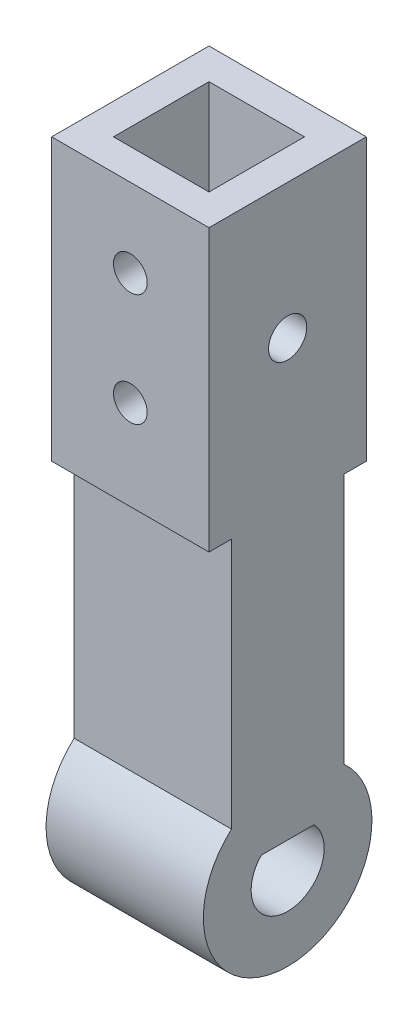
SolidWorks part; units mm, degrees
material "PLA"
ref_plane "Plan de face" through (0, 0, 0) normal (0, 0, 1) x (1, 0, 0)
ref_plane "Plan de dessus" through (0, 0, 0) normal (0, 1, 0) x (1, 0, 0)
ref_plane "Plan de droite" through (0, 0, 0) normal (1, 0, 0) x (0, 0, -1)
sketch "Esquisse1" plane through (0, 0, 0) normal (0, 0, 1) x (1, 0, 0)
  line L1 (0, 0) -> (140, 0) construction
  line L2 (0, 0) -> (0, 155) construction
  line L3 (0, 155) -> (140, 155) construction
  line L4 (140, 0) -> (140, 155) construction
  line L16 (65, 0) -> (65, 121.945)
  line L17 (65, 121.945) -> (0, 145.6031)
  line L18 (0, 145.6031) -> (3.4202, 155)
  line L19 (3.4202, 155) -> (70, 130.7669)
  line L20 (70, 130.7669) -> (136.5798, 155)
  line L21 (136.5798, 155) -> (140, 145.6031)
  line L22 (140, 145.6031) -> (75, 121.945)
  line L23 (75, 121.945) -> (75, 0)
  line L24 (75, 0) -> (65, 0)
  point P19 (70, 0)
  dimension "D1" = 140
  dimension "D2" = 155
  dimension "D3" = 10
  dimension "D4" = 70
  dimension "D5" = 110
  dimension "D6" = 110
  dimension "D7" = 140
  dimension "D8" = 10
  dimension "D9" = 10
  dimension "D10" = 70
extrude "Boss.-Extru.1" add sketch "Esquisse1" along normal blind 10
sketch "Esquisse2" plane through (0, 0, 0) normal (0, 0, -1) x (-1, 0, 0)
  line L0 (-75, 121.945) -> (-140, 145.6031) construction
  line L1 (-140, 145.6031) -> (-136.5798, 155) construction
  line L2 (-136.5798, 155) -> (-70, 130.7669) construction
  line L3 (-135.3015, 143.893) -> (-140, 145.6031)
  line L4 (-140, 145.6031) -> (-136.5798, 155)
  line L5 (-136.5798, 155) -> (-127.1829, 151.5798)
  line L6 (-128.893, 146.8813) -> (-127.1829, 151.5798)
  line L7 (0, 145.6031) -> (-65, 121.945) construction
  line L8 (-70, 130.7669) -> (-3.4202, 155) construction
  line L9 (-3.4202, 155) -> (0, 145.6031) construction
  line L10 (0, 145.6031) -> (-4.6985, 143.893)
  line L11 (-12.8171, 151.5798) -> (-3.4202, 155)
  line L12 (-3.4202, 155) -> (0, 145.6031)
  line L13 (-12.8171, 151.5798) -> (-11.107, 146.8813)
  line L14 (-135.3015, 143.893) -> (-128.893, 146.8813)
  line L15 (-11.107, 146.8813) -> (-4.6985, 143.893)
  dimension "D1" = 10
  dimension "D2" = 10
  dimension "D3" = 5
  dimension "D4" = 5
  dimension "D5" = 5
  dimension "D6" = 5
extrude "Boss.-Extru.2" add sketch "Esquisse2" along normal blind 15
fillet "Congé1" radius 20 3 edges at (75, 121.945, 5) (65, 121.945, 5) (70, 130.7669, 5)
fillet "Congé2" radius 4 2 edges at (138.2899, 150.3015, 10) (1.7101, 150.3015, 10)
sketch "Esquisse3" plane through (65, 0, 0) normal (-1, 0, 0) x (0, 0, 1)
  line L0 (5, 0) -> (5, 33.6289) construction
  line L1 (10, 0) -> (0, 0) construction
  circle A0 centre (5, 0) radius 7.5
  dimension "D1" = 15
extrude "Boss.-Extru.3" add sketch "Esquisse3" against normal up to surface (10 mm away) up to face at (75, 53.9704, 5)
sketch "Esquisse7" plane through (0, 0, 10) normal (0, 0, 1) x (1, 0, 0)
  line L0 (3.4202, 155) -> (0, 145.6031)
  line L1 (0, 145.6031) -> (51.8404, 126.7347)
  line L2 (65, 107.9409) -> (65, 27.9409)
  line L3 (65, 107.9409) -> (65, 5.5902) construction
  line L4 (65, 27.9409) -> (75, 27.9409)
  line L5 (75, 5.5902) -> (75, 107.9409) construction
  line L6 (75, 27.9409) -> (75, 107.9409)
  line L7 (88.1596, 126.7347) -> (140, 145.6031)
  line L8 (140, 145.6031) -> (136.5798, 155)
  line L9 (136.5798, 155) -> (76.8404, 133.2566)
  line L10 (63.1596, 133.2566) -> (3.4202, 155)
  arc A0 (51.8404, 126.7347) -> (65, 107.9409) centre (45, 107.9409) cw
  arc A1 (75, 107.9409) -> (88.1596, 126.7347) centre (95, 107.9409) cw
  arc A2 (76.8404, 133.2566) -> (63.1596, 133.2566) centre (70, 152.0505) cw
  dimension "D1" = 80
extrude "Enlèv. mat.-Extru.1" cut sketch "Esquisse7" against normal up to surface (25 mm away) up to face at (133.5914, 148.5914, -15)
sketch "Esquisse11" plane through (0, 27.9409, 0) normal (0, 1, 0) x (1, 0, 0)
  line L0 (65, 0) -> (65, -10) construction
  line L1 (61, 2) -> (75, 2)
  line L2 (61, 2) -> (61, -12)
  line L3 (61, -12) -> (75, -12)
  line L4 (75, 2) -> (75, -12)
  line L5 (65, -10) -> (75, -10) construction
  dimension "D1" = 14
  dimension "D2" = 14
  dimension "D3" = 4
  dimension "D4" = 2
extrude "Boss.-Extru.4" add sketch "Esquisse11" along normal blind 25
sketch "Esquisse12" plane through (0, 52.9409, 0) normal (0, 1, 0) x (1, 0, 0)
  line L0 (68, 2) -> (68, -12) construction
  line L1 (63.75, -0.75) -> (72.25, -0.75)
  line L2 (63.75, -0.75) -> (63.75, -9.25)
  line L3 (63.75, -9.25) -> (72.25, -9.25)
  line L4 (72.25, -0.75) -> (72.25, -9.25)
  line L5 (75, 2) -> (61, 2) construction
  line L6 (61, -12) -> (75, -12) construction
  line L7 (61, -5) -> (75, -5) construction
  line L8 (61, 2) -> (61, -12) construction
  line L9 (75, -12) -> (75, 2) construction
  line L10 (68, -0.75) -> (68, -9.25) construction
  line L11 (63.75, -5) -> (72.25, -5) construction
  dimension "D1" = 8.5
  dimension "D2" = 8.5
extrude "Enlèv. mat.-Extru.4" cut sketch "Esquisse12" against normal blind 20
sketch "Esquisse13" plane through (61, 0, 0) normal (-1, 0, 0) x (0, 0, 1)
  line L2 (12, 52.9409) -> (12, 27.9409) construction
  line L3 (-2, 52.9409) -> (12, 52.9409) construction
  circle A0 centre (5, 40.9409) radius 1.5
  dimension "D3" = 3
  dimension "D1" = 12
  dimension "D2" = 7
extrude "Enlèv. mat.-Extru.5" cut sketch "Esquisse13" against normal up to surface (14 mm away) up to face at (75, 26.9669, 5)
sketch "Esquisse4" plane through (65, 0, 0) normal (-1, 0, 0) x (0, 0, 1)
  line L7 (5, 0) -> (5, 7.4852) construction
  line L11 (2.6548, 2.25) -> (7.3452, 2.25)
  line L12 (0.3981, -3.25) -> (8.2082, -3.25) construction
  arc A1 (2.6548, 2.25) -> (7.3452, 2.25) centre (5, 0) ccw
  point P10 (5, 6)
  point P11 (5, 6)
  dimension "D1" = 6.5
  dimension "D2" = 5.5
extrude "Enlèv. mat.-Extru.2" cut sketch "Esquisse4" against normal blind 20
sketch "Esquisse15" plane through (0, 0, 12) normal (0, 0, 1) x (1, 0, 0)
  line L0 (75, 52.9409) -> (75, 27.9409) construction
  line L1 (61, 52.9409) -> (75, 52.9409) construction
  line L2 (61, 27.9409) -> (75, 27.9409) construction
  circle A1 centre (68, 45.9409) radius 1.5
  circle A2 centre (68, 35.9409) radius 1.5
  dimension "D5" = 3
  dimension "D6" = 3
  dimension "D1" = 7
  dimension "D2" = 7
  dimension "D3" = 7
  dimension "D4" = 8
extrude "Enlèv. mat.-Extru.6" cut sketch "Esquisse15" against normal up to surface (14 mm away) up to face at (68, 40.4409, -2)
hole_wizard "Dégagement M31" positions "Esquisse16" profile "Esquisse17" hole size "M3" standard "ISO"
sketch "Esquisse16" plane through (0, 0, -2) normal (0, 0, -1) x (-1, 0, 0)
  point P0 (-68, 45.9409)
  point P3 (-68, 35.9409)
sketch "Esquisse17" plane through (68, 45.9409, -2) normal (1, 0, 0) x (0, 1, 0)
  line L0 (0, 0) -> (0, 11.0215)
  line L1 (0, 11.0215) -> (1.7, 10)
  line L2 (1.7, 10) -> (1.7, 0)
  line L5 (1.7, 0) -> (0, 0)
  line L10 (0, 11.0215) -> (-1.7, 10) construction
  line L11 (0, -6.35) -> (0, 107.95) construction
  dimension "Diamètre du perçage" = 3.4
  dimension "Profondeur du perçage" = 10
  dimension "Angle de pointe" = 118
hole_wizard "Dégagement M32" positions "Esquisse18" profile "Esquisse19" hole size "M3" standard "ISO"
sketch "Esquisse18" plane through (75, 0, 0) normal (1, 0, 0) x (0, 0, -1)
  point P0 (-5, 40.9409)
sketch "Esquisse19" plane through (75, 40.9409, 5) normal (0, 1, 0) x (0, 0, -1)
  line L0 (0, 0) -> (0, 11.0215)
  line L1 (0, 11.0215) -> (1.7, 10)
  line L2 (1.7, 10) -> (1.7, 0)
  line L5 (1.7, 0) -> (0, 0)
  line L10 (0, 11.0215) -> (-1.7, 10) construction
  line L11 (0, -6.35) -> (0, 107.95) construction
  dimension "Diamètre du perçage" = 3.4
  dimension "Profondeur du perçage" = 10
  dimension "Angle de pointe" = 118
sketch "Esquisse20" plane through (65, 0, 0) normal (-1, 0, 0) x (0, 0, 1)
  line L0 (10, 5.5902) -> (10, 27.9409)
  line L1 (-2, 27.9409) -> (12, 27.9409) construction
  line L2 (10, 27.9409) -> (10, 5.5902) construction
  line L3 (10, 27.9409) -> (0, 27.9409)
  line L4 (0, 27.9409) -> (0, 5.5902)
  line L5 (7.3452, 2.25) -> (2.6548, 2.25)
  arc A0 (0, 5.5902) -> (10, 5.5902) centre (5, 0) ccw
  arc A1 (2.6548, 2.25) -> (7.3452, 2.25) centre (5, 0) ccw
extrude "Boss.-Extru.6" add sketch "Esquisse20" along normal blind 4
equation "\"long_tot\"=155"
equation "\"espac_sub_arms\"= 120"
equation "\"épaiss_cadre\"=10"
equation "\"long_protub\"= 15"
equation "\"rayon_conge\"= 3"
equation "\"diam_axe\"= 5"
equation "\"D1@Esquisse1\"=\"espac_sub_arms\"+\"épaiss_cadre\"*2"
equation "\"D2@Esquisse1\"=\"long_tot\""
equation "\"D3@Esquisse1\"=\"épaiss_cadre\""
equation "\"D4@Esquisse1\"=\"D1@Esquisse1\"/2"
equation "\"D6@Esquisse1\"=\"D5@Esquisse1\""
equation "\"D8@Esquisse1\"=\"épaiss_cadre\""
equation "\"D9@Esquisse1\"=\"épaiss_cadre\""
equation "\"D10@Esquisse1\"=\"D4@Esquisse1\""
equation "\"D1@Boss.-Extru.1\"=\"épaiss_cadre\""
equation "\"D2@Esquisse2\"=\"épaiss_cadre\""
equation "\"D1@Boss.-Extru.2\"=\"long_protub\""
equation "\"D1@Esquisse2\"=\"épaiss_cadre\""
equation "\"D3@Esquisse2\"=\"D1@Esquisse2\"/2"
equation "\"D4@Esquisse2\"=\"D1@Esquisse2\"/2"
equation "\"D5@Esquisse2\"=\"D2@Esquisse2\"/2"
equation "\"D6@Esquisse2\"=\"D2@Esquisse2\"/2"
